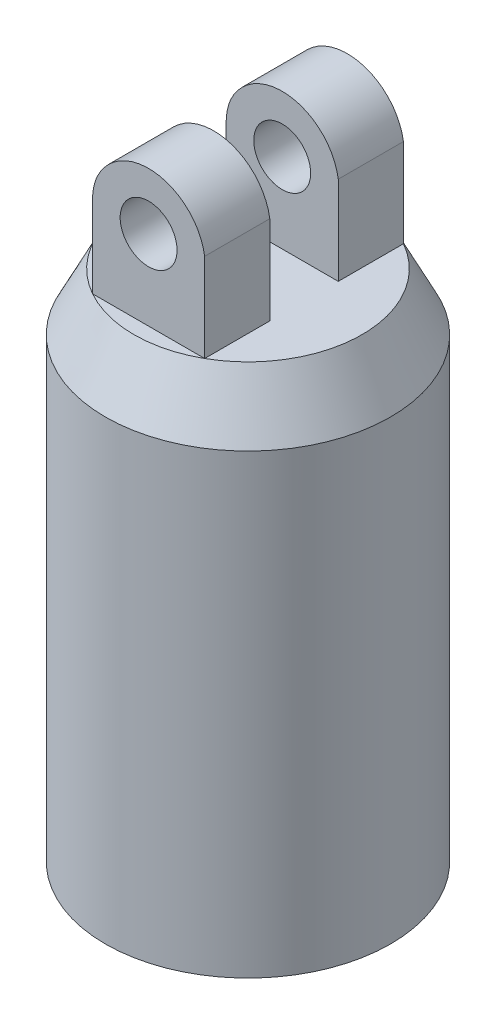
SolidWorks part; units mm, degrees
ref_plane "Спереди" through (0, 0, 0) normal (0, 0, 1) x (1, 0, 0)
ref_plane "Сверху" through (0, 0, 0) normal (0, 1, 0) x (1, 0, 0)
ref_plane "Справа" through (0, 0, 0) normal (1, 0, 0) x (0, 0, -1)
sketch "Эскиз1" plane through (0, 0, 0) normal (0, 1, 0) x (1, 0, 0)
  line L0 (0, 0) -> (0, 15.2272) construction
  line L1 (0, 0) -> (0, -15.2272) construction
  line L2 (-2.4581, 0) -> (0, 0) construction
  line L3 (0, 0) -> (0.6254, 0) construction
  circle A0 centre (0, 0) radius 12.5
  circle A1 centre (0, 0) radius 5
  point P8 (0, 0)
  dimension "D1" = 25
extrude "Бобышка-Вытянуть1" add sketch "Эскиз1" along normal blind 40
sketch "Эскиз4" plane through (0, 0, 0) normal (1, 0, 0) x (0, 0, -1)
  line L0 (0, 39.9999) -> (0, 47.4013) construction
  line L1 (0, 47.4013) -> (0, 52.8542) construction
  line L2 (0, 39.9999) -> (12.5, 40) construction
  line L3 (12.5, 40) -> (1.8247, 39.9999) construction
  line L4 (0, 39.9999) -> (-12.5, 40) construction
  line L5 (-10, 45) -> (0, 45)
  line L6 (-12.5, 40) -> (0, 39.9999)
  line L7 (0, 39.9999) -> (0, 45)
  line L8 (-12.5, 40) -> (-10, 45)
  dimension "D1" = 10
revolve "Повернуть2" add sketch "Эскиз4" angle 360 about L7
sketch "Эскиз9" plane through (0, 45, 0) normal (0, 1, 0) x (1, 0, 0)
  line L0 (-4.9142, 8.7092) -> (-4.9142, -8.7092)
  line L1 (-4.9142, 8.7092) -> (4.9142, 8.7092)
  line L3 (-4.9142, -8.7092) -> (4.9142, -8.7092)
  line L5 (-4.9142, 8.7092) -> (4.9142, -8.7092) construction
  line L6 (-4.9142, -8.7092) -> (4.9142, 8.7092) construction
  line L7 (4.9142, 8.7092) -> (4.9142, -8.7092)
  circle A0 centre (0, 0) radius 10 construction
  circle A1 centre (0, 0) radius 10
  point P0 (0, 0)
extrude "Бобышка-Вытянуть4" add sketch "Эскиз9" along normal blind 15 contours L7 L1 L0 L3 region at (0, 45, 0)
sketch "Эскиз12" plane through (0, 0, 8.7092) normal (0, 0, 1) x (1, 0, 0)
  line L0 (0, 60) -> (0, 45) construction
  line L1 (-4.9142, 60) -> (4.9142, 60) construction
  line L2 (-4.9142, 45) -> (4.9142, 45) construction
  line L3 (-4.9142, 52.1462) -> (-4.9142, 60)
  line L4 (-4.9142, 60) -> (4.9142, 60)
  line L5 (4.9142, 60) -> (4.9142, 52.5)
  line L6 (4.9142, 60) -> (4.9142, 45) construction
  circle A1 centre (0, 52) radius 2.493
  circle A2 centre (0, 52.1462) radius 4.9142
  line M6 (-4.9142, 60) -> (-4.9142, 45)
  dimension "D1" = 7
extrude "Вырез-Вытянуть2" cut sketch "Эскиз12" against normal through all contours A1
extrude "Вырез-Вытянуть3" cut sketch "Эскиз12<4>" against normal through all contours L0 L4 A2 M6 region at (-2.8161, 57.8523, 8.7092)
sketch "Эскиз12<4>" plane through (0, 0, 8.7092) normal (0, 0, 1) x (1, 0, 0) same geometry as "Эскиз12"
sketch "Эскиз14" plane through (0, 0, 8.7092) normal (0, 0, 1) x (1, 0, 0)
  line L0 (4.9142, 52.5) -> (4.9142, 53.8458)
  line L1 (4.9142, 60) -> (4.9142, 45) construction
  line L2 (4.9142, 60) -> (0, 60)
  line L3 (0, 60) -> (0, 57.0605)
  line L4 (0, 57.0605) -> (0, 60)
  line L5 (4.9142, 60) -> (4.9142, 52.5)
  circle A0 centre (0, 52) radius 4.9724
  line M7 (0, 60) -> (0, 57.0605)
  arc M8 (0, 57.0605) -> (-4.9142, 52.1462) centre (0, 52.1462) ccw
  line M11 (4.9142, 45) -> (4.9142, 60)
  line M12 (4.9142, 60) -> (0, 60)
extrude "Вырез-Вытянуть4" cut sketch "Эскиз14" against normal through all contours A0 L5 M11 M12 M7 M8 region at (2.7213, 57.8128, 8.7092)
sketch "Эскиз15" plane through (4.9142, 0, 0) normal (1, 0, 0) x (0, 0, -1)
  line L0 (-3, 45) -> (-3, 52.7583)
  line L1 (8.7092, 45) -> (-8.7092, 45) construction
  line L2 (8.7092, 52.7583) -> (-8.7092, 52.7583) construction
  line L3 (-3, 52.7583) -> (-3, 60.738)
  line L4 (0, 45) -> (0, 68.1109) construction
  line L5 (3, 45) -> (3, 60.738)
  line L6 (3, 60.738) -> (-3, 60.738)
  line L7 (-3, 45) -> (0, 45)
  line L8 (0, 45) -> (3, 45)
  dimension "D1" = 6
extrude "Вырез-Вытянуть5" cut sketch "Эскиз15" against normal blind 15
